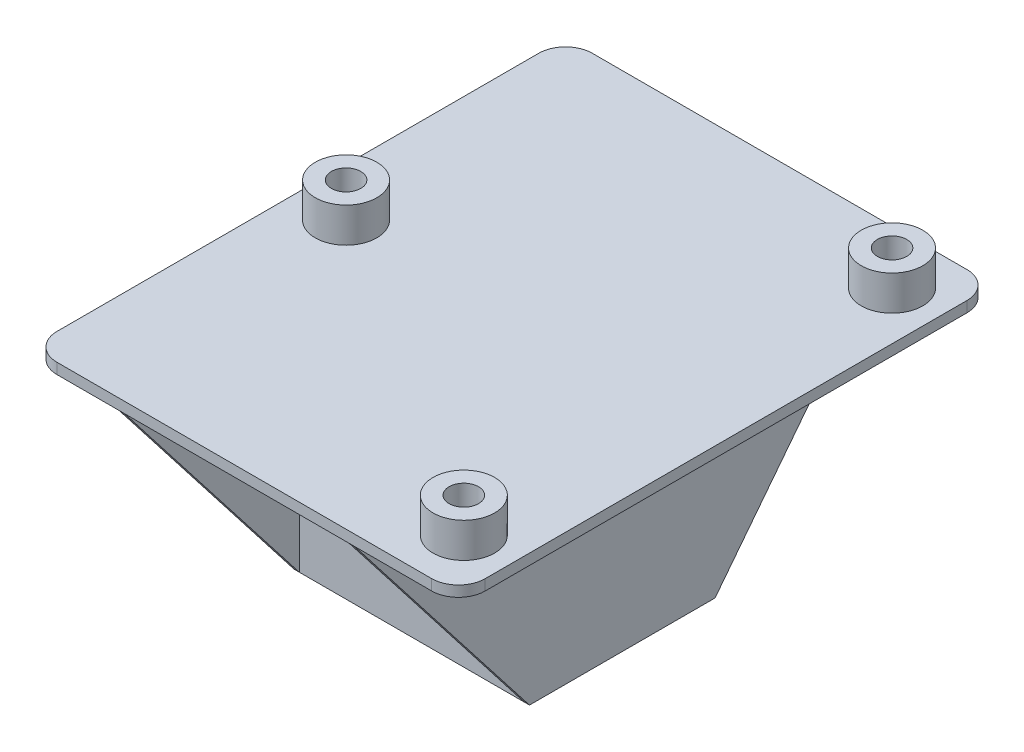
SolidWorks part; units mm, degrees
material "ABS"
ref_plane "Front Plane" through (0, 0, 0) normal (0, 0, 1) x (1, 0, 0)
ref_plane "Top Plane" through (0, 0, 0) normal (0, 1, 0) x (1, 0, 0)
ref_plane "Right Plane" through (0, 0, 0) normal (1, 0, 0) x (0, 0, -1)
sketch "Sketch1" plane through (0, 0, 0) normal (0, 1, 0) x (1, 0, 0)
  line L10 (-35, 50) -> (35, 50)
  line L11 (-40, 45) -> (-40, -45)
  line L12 (-35, -50) -> (35, -50)
  line L13 (40, 45) -> (40, -45)
  line L14 (-40, 50) -> (40, -50) construction
  line L15 (-40, -50) -> (40, 50) construction
  arc A0 (35, 50) -> (40, 45) centre (35, 45) cw
  arc A1 (35, -50) -> (40, -45) centre (35, -45) ccw
  arc A2 (-40, -45) -> (-35, -50) centre (-35, -45) ccw
  arc A3 (-35, 50) -> (-40, 45) centre (-35, 45) ccw
  point P0 (0, 0)
  dimension "D3" = 5
  dimension "D1" = 80
  dimension "D2" = 100
extrude "Boss-Extrude1" add sketch "Sketch1" along normal blind 2
sketch "Sketch2" plane through (0, 2, 0) normal (0, 1, 0) x (1, 0, 0)
  line L0 (-31, 0) -> (0, 0) construction
  line L1 (0, 0) -> (31, 0) construction
  line L2 (31, 40) -> (31, -40) construction
  line L4 (-31, 0) -> (-40, 0) construction
  line L5 (-40, 45) -> (-40, -45) construction
  line L6 (31, 0) -> (40, 0) construction
  line L7 (40, -45) -> (40, 45) construction
  circle A0 centre (-31, 0) radius 2.75
  circle A1 centre (31, 40) radius 2.75
  circle A2 centre (31, -40) radius 2.75
  dimension "D4" = 5.5
  dimension "D1" = 62
  dimension "D3" = 80
extrude "Cut-Extrude1" cut sketch "Sketch2" against normal through all
sketch "Sketch3" plane through (0, 2, 0) normal (0, 1, 0) x (1, 0, 0)
  circle A0 centre (31, -40) radius 2.75 construction
  circle A1 centre (-31, 0) radius 2.75 construction
  circle A2 centre (31, 40) radius 2.75 construction
  circle A3 centre (31, -40) radius 2.75
  circle A4 centre (-31, 0) radius 2.75
  circle A5 centre (31, 40) radius 2.75
  circle A6 centre (-31, 0) radius 5.75
  circle A7 centre (31, 40) radius 5.75
  circle A8 centre (31, -40) radius 5.75
  dimension "D1" = 3
extrude "Boss-Extrude3" add sketch "Sketch3<2>" along normal blind 6.5
sketch "Sketch3<2>" plane through (0, 2, 0) normal (0, 1, 0) x (1, 0, 0) same geometry as "Sketch3"
sketch "Sketch6" plane through (0, 2, 0) normal (0, 1, 0) x (1, 0, 0)
  line L0 (-36.4704, -29.7789) -> (28.5296, -49.7789)
  line L1 (-40, 45) -> (-40, -45) construction
  line L2 (-35, -50) -> (35, -50) construction
  line L3 (-40, 0) -> (40, 0) construction
  line L4 (40, -45) -> (40, 45) construction
  line L5 (-40, -25) -> (-40, -50)
  line L6 (-40, -50) -> (30, -50)
  line L7 (-40, 50) -> (30, 50)
  line L8 (-40, 25) -> (-40, 50)
  line L9 (-36.4704, 29.7789) -> (28.5296, 49.7789)
  arc A1 (-40, -25) -> (-36.4704, -29.7789) centre (-35, -25) ccw
  arc A2 (28.5296, -49.7789) -> (30, -50) centre (30, -45) ccw
  arc A3 (28.5296, 49.7789) -> (30, 50) centre (30, 45) cw
  arc A4 (-40, 25) -> (-36.4704, 29.7789) centre (-35, 25) cw
  dimension "D1" = 10
  dimension "D2" = 10
  dimension "D3" = 25
  dimension "D4" = 10
extrude "Boss-Extrude2" add sketch "Sketch3" along normal blind 4.5
sketch "Sketch7" plane through (0, 0, 0) normal (0, -1, 0) x (1, 0, 0)
  line L0 (19.6, 50) -> (20.6, 50)
  line L5 (-23.4, 50) -> (-22.4, 50)
  line L6 (-23.4, 50) -> (-23.4, -50)
  line L7 (-23.4, -50) -> (-22.4, -50)
  line L8 (20.6, 50) -> (20.6, -50)
  line L10 (19.6, -50) -> (19.6, -17.3333)
  line L11 (19.6, -17.3333) -> (-22.4, -17.3333)
  line L12 (-22.4, -50) -> (-22.4, -17.3333)
  line L14 (19.6, 50) -> (19.6, 17.3333)
  line L15 (19.6, 17.3333) -> (-22.4, 17.3333)
  line L16 (-22.4, 50) -> (-22.4, 17.3333)
  line L17 (-22.4, 16.3333) -> (19.6, 16.3333)
  line L18 (-22.4, 16.3333) -> (-22.4, -16.3333)
  line L19 (-22.4, -16.3333) -> (19.6, -16.3333)
  line L20 (19.6, 16.3333) -> (19.6, -16.3333)
  line L21 (19.6, -50) -> (20.6, -50)
  line L23 (-22.4, 17.3333) -> (-22.4, 16.3333) construction
  line L24 (-40, 50) -> (30, 50) construction
  line L25 (-22.4, 16.3333) -> (-23.4, 16.3333) construction
  line L26 (-22.4, -16.3333) -> (-22.4, -17.3333) construction
  point P22 (-23.4, 0)
  dimension "D1" = 19.6
  dimension "D2" = 1
  dimension "D4" = 42
extrude "Boss-Extrude4" add sketch "Sketch7" along normal blind 42
sketch "Sketch8" plane through (-22.4, 0, 0) normal (1, 0, 0) x (0, 0, -1)
  line L0 (-50, 0) -> (-17.3333, -42)
  line L1 (-17.3333, -42) -> (-50, -42)
  line L2 (-50, -42) -> (-50, 0)
  line L3 (17.3333, -42) -> (50, 0)
  line L4 (50, 0) -> (50, -42)
  line L5 (50, -42) -> (17.3333, -42)
extrude "Cut-Extrude2" cut sketch "Sketch8" against normal through all both and the other way through all
sketch "Sketch9" plane through (0, 0, 17.3333) normal (0, 0, 1) x (1, 0, 0)
  line L0 (-1.4, -21) -> (-10.2388, -12.1612) construction
  line L1 (-1.4, -21) -> (-1.4, -42) construction
  line L2 (-22.4, -21) -> (-1.4, -21) construction
  line L3 (-22.4, -42) -> (-22.4, 0) construction
  line L4 (19.6, -42) -> (-22.4, -42) construction
  circle A0 centre (-1.4, -21) radius 5
  circle A1 centre (-10.2388, -12.1612) radius 1.5
  circle A5 centre (-10.2388, -29.8388) radius 1.5
  circle A6 centre (7.4388, -12.1612) radius 1.5
  circle A7 centre (7.4388, -29.8388) radius 1.5
  dimension "D2" = 10
  dimension "D3" = 3
  dimension "D1" = 12.5
  dimension "D4" = 45
extrude "Cut-Extrude3" cut sketch "Sketch9" against normal through all
